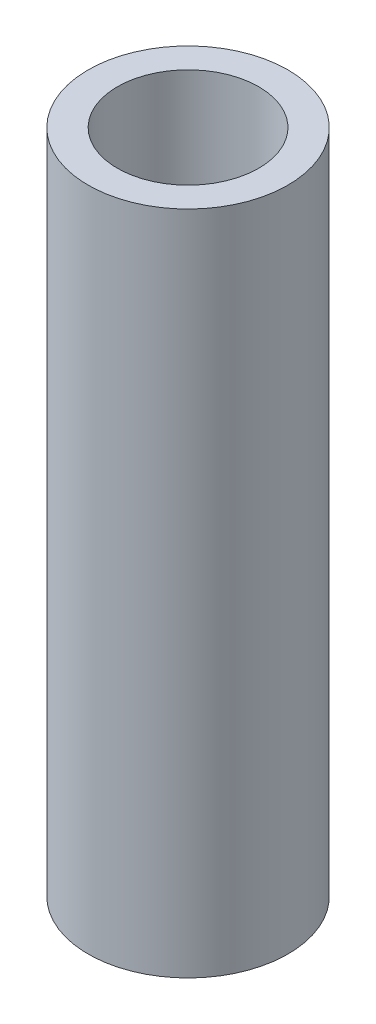
SolidWorks part; units mm, degrees
material "Rubber"
ref_plane "Front Plane" through (0, 0, 0) normal (0, 0, 1) x (1, 0, 0)
ref_plane "Top Plane" through (0, 0, 0) normal (0, 1, 0) x (1, 0, 0)
ref_plane "Right Plane" through (0, 0, 0) normal (1, 0, 0) x (0, 0, -1)
sketch "Sketch1" plane through (0, 0, 0) normal (0, 1, 0) x (1, 0, 0)
  circle A0 centre (0, 0) radius 6.05
extrude "Extrude-Thin1" add sketch "Sketch1" along normal blind 57 thin thin type one direction wall 2.5
